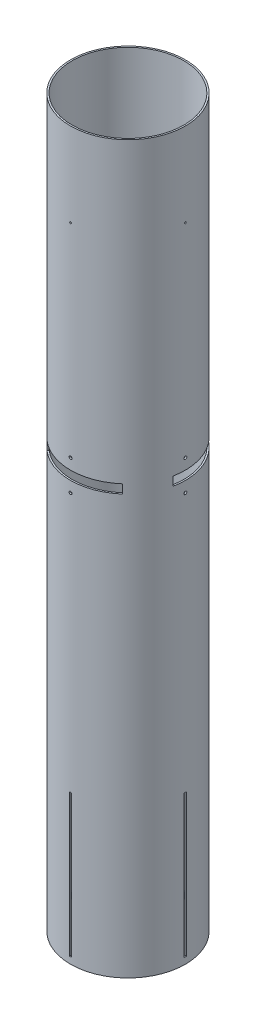
SolidWorks part; units mm, degrees
material "A-Glass Fiber"
ref_plane "Front Plane" through (0, 0, 0) normal (0, 0, 1) x (1, 0, 0)
ref_plane "Top Plane" through (0, 0, 0) normal (0, 1, 0) x (1, 0, 0)
ref_plane "Right Plane" through (0, 0, 0) normal (1, 0, 0) x (0, 0, -1)
sketch "Sketch1" plane through (0, 0, 0) normal (0, 1, 0) x (1, 0, 0)
  circle A0 centre (0, 0) radius 76.2
  circle A1 centre (0, 0) radius 78.359
  dimension "D1" = 152.4
  dimension "D2" = 156.718
extrude "Boss-Extrude1" add sketch "Sketch1" along normal blind 990.6
ref_plane "Plane1" through (0, 0, 0) normal (0.7071, 0, 0.7071) x (0.7071, 0, -0.7071)
ref_axis "Axis1" through (0, 990.6, 0) along (0, -1, 0)
sketch "Sketch2" plane through (0, 0, 0) normal (1, 0, 0) x (0, 0, -1)
  line L0 (0, 0) -> (0, 8.89)
  line L1 (1.5875, 8.89) -> (-1.5875, 8.89)
  line L2 (1.5875, 8.89) -> (1.5875, 203.2)
  line L3 (1.5875, 203.2) -> (-1.5875, 203.2)
  line L4 (-1.5875, 8.89) -> (-1.5875, 203.2)
  line L5 (1.5875, 8.89) -> (-1.5875, 203.2) construction
  line L6 (1.5875, 203.2) -> (-1.5875, 8.89) construction
  line L7 (78.359, 990.6) -> (-78.359, 990.6) construction
  line L8 (78.359, 990.6) -> (-78.359, 990.6)
  line L9 (0, 990.6) -> (0, 598.645)
  line L10 (-78.359, 0) -> (78.359, 0) construction
  circle A0 centre (0, 598.645) radius 2
  circle A1 centre (0, 876.3) radius 1.0922
  point P0 (0, 106.045)
  dimension "D4" = 4
  dimension "D6" = 2.1844
  dimension "D1" = 3.175
  dimension "D2" = 194.31
  dimension "D5" = 598.645
  dimension "D3" = 203.2
  dimension "D7" = 114.3
extrude "Fin Slots" cut sketch "Sketch2" against normal through all contours L4 L1 L2 L3 region at (0, 106.045, 0)
pattern_circular "CirPattern1" count 4 over 360 about axis through (0, 0, 0) along (0, 1, 0) of "Fin Slots" reverse direction yes
extrude "Cut-Extrude2" cut sketch "Sketch2<3>" against normal through all contours A0 region at (0, 600.0192, -1.3742)
sketch "Sketch2<3>" plane through (0, 0, 0) normal (1, 0, 0) x (0, 0, -1) same geometry as "Sketch2"
pattern_circular "CirPattern2" count 4 over 360 about axis through (0, 990.6, 0) along (0, -1, 0) of "Cut-Extrude2"
sketch "Sketch3" plane through (0, 0, 0) normal (0.7071, 0, 0.7071) x (0.7071, 0, -0.7071)
  line L0 (0, 0) -> (0, 127) construction
  circle A0 centre (0, 127) radius 3.175
  dimension "D1" = 6.35
  dimension "D2" = 127
extrude "Cut-Extrude3" cut sketch "Sketch3" against normal through all
ref_plane "Plane3" through (0, 583.8825, 0) normal (0, 1, 0) x (1, 0, 0)
sketch "Sketch7" plane through (0, 583.8825, 0) normal (0, 1, 0) x (1, 0, 0)
  line L0 (0, 0) -> (-76.8534, -15.2871)
  line L1 (0, 0) -> (0, 93.232) construction
  line L2 (0, 0) -> (-25.1877, 74.2005)
  line L3 (-78.359, 0) -> (0, 0) construction
  arc A0 (-78.3335, 2) -> (-78.3335, -2) centre (0, 0) ccw construction
  circle A1 centre (0, 0) radius 76.2 construction
  circle A2 centre (0, 0) radius 78.359
  circle A3 centre (0, 0) radius 78.359
  circle A4 centre (0, 0) radius 76.2
  circle A5 centre (0, 0) radius 78.359 construction
  arc A6 (2, 78.3335) -> (-2, 78.3335) centre (0, 0) ccw construction
  arc A7 (-78.3335, 2) -> (-78.3335, -2) centre (0, 0) ccw
  arc A8 (2, 78.3335) -> (-2, 78.3335) centre (0, 0) ccw
  dimension "D1" = 82.5
  dimension "D3" = 11.25
  dimension "D2" = 0
extrude "Cut-Extrude4" cut sketch "Sketch7" against normal blind 12.065 contours A4 A3 L0 region at (-75.9984, 583.8825, 14.0521)
pattern_circular "CirPattern3" count 3 over 360 about axis through (0, 990.6, 0) along (0, -1, 0) of "Cut-Extrude4"
extrude "Shear Screw Holes" cut sketch "Sketch2<4>" against normal through all contours L9 A1 | L9 A1 region at (0, 876.3, -0.4635) region at (0, 876.3, 0.4635)
sketch "Sketch2<4>" plane through (0, 0, 0) normal (1, 0, 0) x (0, 0, -1) same geometry as "Sketch2"
pattern_circular "Shear Screw Pattern" count 4 over 360 about axis through (0, 990.6, 0) along (0, -1, 0) of "Shear Screw Holes"
pattern_linear "LPattern1" count 2 spacing 41.524 along (0, -1, 0) of "Cut-Extrude2", "CirPattern2"
equation "\"D1@Boss-Extrude1\" = \"Aft_Section_Length\""
equation "\"AB_Coupler_OD_Length\"= 1in"
equation "\"AB_Coupling_Section_Length\"= 0.375in"
equation "\"AB_Coupler_Length\"= \"AB_Coupler_OD_Length\" + \"AB_Coupling_Section_Length\" * 2"
equation "\"AB_Coupler_Num_Screws\"= 4"
equation "\"AB_Coupling_Screw_Diameter\"= 0.15748in"
equation "\"Aft_Section_Length\"= 39in"
equation "\"D4@Sketch2\"=\"AB_Coupling_Screw_Diameter\""
equation "\"D1@CirPattern2\"=\"AB_Coupler_Num_Screws\""
equation "\"Rail_Nut_From_Bottom\"= 5in"
equation "\"Rail_Nut_Diam\"= 0.25in"
equation "\"D1@Sketch3\"=\"Rail_Nut_Diam\""
equation "\"D2@Sketch3\"=\"Rail_Nut_From_Bottom\""
equation "\"AB_BKHD_Thickness\"= 0.375in"
equation "\"AB_Mount_From_Bottom\"= 23.175in"
equation "\"Cutout_Angle\"= 80"
equation "\"Shear_Screw_Diameter\"= 0.086in"
equation "\"D6@Sketch2\"=\"Shear_Screw_Diameter\""
equation "\"Shear_Screw_Coupler_Location\"= 4.5in"
equation "\"D7@Sketch2\"=\"Shear_Screw_Coupler_Location\""
equation "\"Bodytube_OD\"= 6.17in"
equation "\"Bodytube_ID\"= 5.998in"
equation "\"Motor_OD\"= 4in"
equation "\"Fwd_Tube_Length\"= 40in"
equation "\"Mid_Tube_Length\"= 1in"
equation "\"Mid_Coupler_Length\"= 13in"
equation "\"AB_Paddle_Height\"= 0.375in"
equation "\"Num_Cutouts\"= 3"
equation "\"AB_Coupler_OD\"= 6.17in"
equation "\"AB_Coupler_ID\"= 5.75in"
equation "\"AB_Coupler_Surface_Diameter\"= 5.998in"
equation "\"AB_Central_Bushing_Length\"= .4724in"
equation "\"Lead_Screw_Dist\"= 3.4in"
equation "\"Lead_Screw_Diam\"= 0.386in"
equation "\"Lead_Screw_Length\"= (\"Mid_Coupler_Length\" + 2*0.375in + 2*0.5in)"
equation "\"Paddle_Pin_Offset\"= .25in"
equation "\"Paddle_Pin_Radius\"= 2.25in"
equation "\"SS_Paddle_Pin_Radius\"= 2.25*0.66in"
equation "\"Paddle_Gear_OD\"= 3.2in"
equation "\"Drive_Gear_OD\"= 1.7in"
equation "\"Fwd_BKHD_From_Top\"= 18in"
equation "\"Fin_Thickness\"= .118in"
equation "\"Guiderail_Cutout_Diameter\"= 1.5in"
equation "\"DB9_Hole_Dist\"= 25mm"
equation "\"DB9_Relief_Width\"= 0.47in"
equation "\"DB9_Relief_Hole_Offset\"= 0.09in"
equation "\"Airbrakes_Wire_Hole_Dia\"= .25in"
equation "\"Airbrakes_Wire_Hole_Dist\"= 1.1in"
equation "\"Servo_Gear_Offset\"= 0.5in"
equation "\"D3@LPattern1\"=\"AB_Central_Bushing_Length\"+\"AB_Coupling_Section_Length\"+0.787402"
